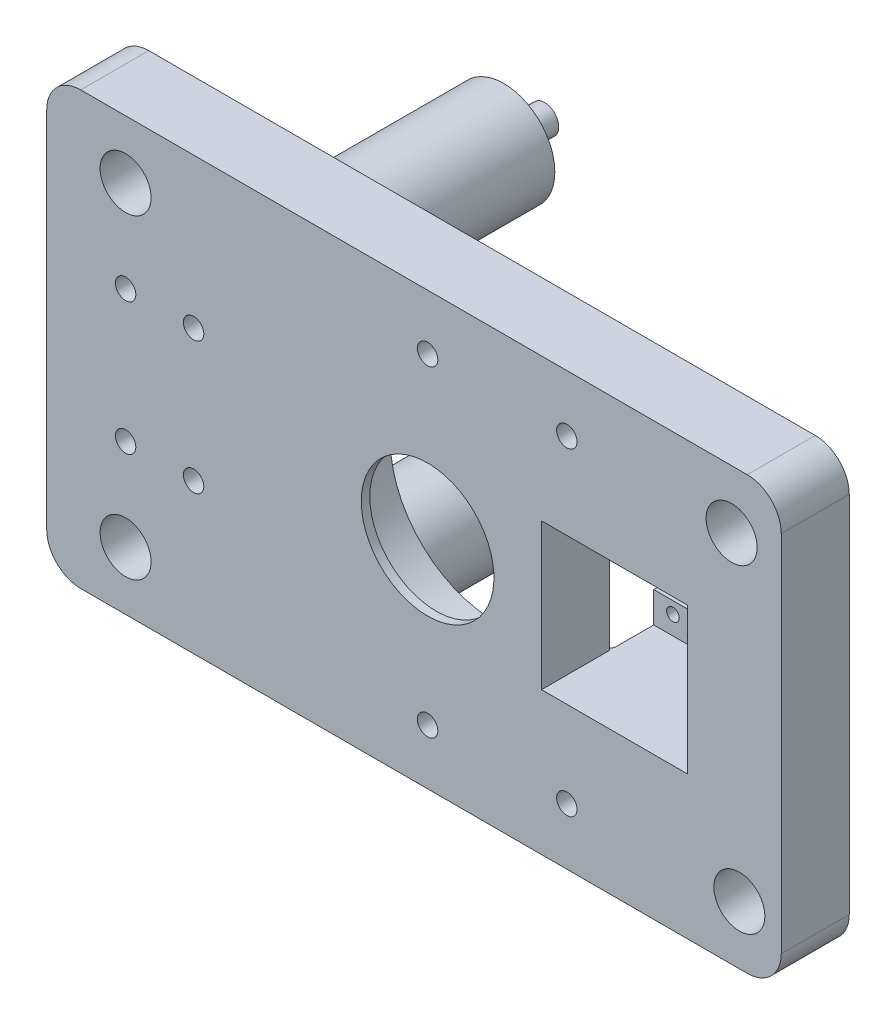
SolidWorks part; units mm, degrees
ref_plane "Front Plane" through (0, 0, 0) normal (0, 0, 1) x (1, 0, 0)
ref_plane "Top Plane" through (0, 0, 0) normal (0, 1, 0) x (1, 0, 0)
ref_plane "Right Plane" through (0, 0, 0) normal (1, 0, 0) x (0, 0, -1)
sketch "Sketch1" plane through (0, 0, 0) normal (0, 0, 1) x (1, 0, 0)
  line L1 (-108, 63.5) -> (108, 63.5)
  line L2 (-108, 63.5) -> (-108, -63.5)
  line L3 (-108, -63.5) -> (108, -63.5)
  line L4 (108, 63.5) -> (108, -63.5)
  line L5 (-108, 63.5) -> (108, -63.5) construction
  line L6 (-108, -63.5) -> (108, 63.5) construction
  point P0 (0, 0)
  dimension "D1" = 127
  dimension "D2" = 216
extrude "Boss-Extrude1" add sketch "Sketch1" along normal blind 20
fillet "Fillet1" radius 10 1 edges at (-108, 63.5, 10)
fillet "Fillet2" radius 10 3 edges at (-108, -63.5, 10) (108, 63.5, 10) (108, -63.5, 10)
sketch "Sketch9" plane through (0, 0, 0) normal (0, 0, -1) x (-1, 0, 0)
  line L0 (-98, 63.5) -> (98, 63.5) construction
  line L1 (-37.5, -21.5) -> (-80.5, -21.5)
  line L2 (-37.5, -21.5) -> (-37.5, 21.5)
  line L3 (-37.5, 21.5) -> (-80.5, 21.5)
  line L4 (-80.5, -21.5) -> (-80.5, 21.5)
  line L5 (-37.5, -21.5) -> (-80.5, 21.5) construction
  line L6 (-37.5, 21.5) -> (-80.5, -21.5) construction
  line L8 (108, 0) -> (-108, 0) construction
  line L9 (108, 53.5) -> (108, -53.5) construction
  line L10 (-108, -53.5) -> (-108, 53.5) construction
  circle A0 centre (-4, 0) radius 31
  point P2 (-59, 0)
  dimension "D6" = 62
  dimension "D1" = 27.5
  dimension "D2" = 55
  dimension "D3" = 43
  dimension "D4" = 43
  dimension "D5" = 63.5
extrude "Cut-Extrude4" cut sketch "Sketch9" against normal blind 17.5 contours A0
sketch "Sketch12" plane through (0, 0, 17.5) normal (0, 0, -1) x (-1, 0, 0)
  circle A0 centre (-4, 0) radius 19.5
  dimension "D1" = 39
extrude "Cut-Extrude5" cut sketch "Sketch12" against normal through all
extrude "Cut-Extrude6" cut sketch "Sketch9<4>" against normal through all contours L3 L4 L1 L2
sketch "Sketch9<4>" plane through (0, 0, 0) normal (0, 0, -1) x (-1, 0, 0) same geometry as "Sketch9"
sketch "Sketch13" plane through (0, 0, 0) normal (0, 0, -1) x (-1, 0, 0)
  line L1 (-37.5, -21.5) -> (-80.5, -21.5)
  line L2 (-37.5, -21.5) -> (-37.5, -25.5)
  line L3 (-37.5, -25.5) -> (-80.5, -25.5)
  line L4 (-80.5, -21.5) -> (-80.5, -25.5)
  dimension "D1" = 4
  dimension "D2" = 43
extrude "Boss-Extrude2" add sketch "Sketch13" along normal blind 17
ref_plane "Plane3" through (0, -21.5, 0) normal (0, 1, 0) x (1, 0, 0)
ref_plane "Plane4" through (0, 0, 0) normal (0, 0, -1) x (-1, 0, 0)
ref_plane "Plane6" through (80.5, 0, 0) normal (1, 0, 0) x (0, 0, -1)
sketch "Sketch16" plane through (80.5, 0, 0) normal (1, 0, 0) x (0, 0, -1)
  line L0 (17, -21.5) -> (0, -21.5) construction
  line L1 (17.0075, -21.5) -> (0.1109, -21.5)
  line L2 (17.0075, -21.5) -> (17.0075, -25.5)
  line L3 (17.0075, -25.5) -> (0.1109, -25.5)
  line L4 (0.1109, -21.5) -> (0.1109, -25.5)
  line L5 (17, -25.5) -> (0, -25.5) construction
fillet "Fillet4" radius 2 3 edges at (59, -25.5, 0) (37.5, -23.5, 0) (80.5, -23.5, 0)
sketch "Sketch17" plane through (0, -21.5, 0) normal (0, 1, 0) x (1, 0, 0)
  line L0 (80.5, 17.0075) -> (80.5, 0.1109) construction
  line L1 (37.5, 17) -> (80.5, 17)
  line L2 (37.5, 17) -> (37.5, 13)
  line L3 (37.5, 13) -> (80.5, 13)
  line L4 (80.5, 17) -> (80.5, 13)
  dimension "D1" = 4
extrude "Boss-Extrude5" add sketch "Sketch17" along normal blind 9
sketch "Sketch18" plane through (0, 0, 0) normal (0, 0, -1) x (-1, 0, 0)
  line L1 (-37.5, 21.5) -> (-80.5, 21.5)
  line L2 (-37.5, 21.5) -> (-37.5, 25.5)
  line L3 (-37.5, 25.5) -> (-80.5, 25.5)
  line L4 (-80.5, 21.5) -> (-80.5, 25.5)
  dimension "D1" = 43
  dimension "D2" = 4
extrude "Boss-Extrude6" add sketch "Sketch18" along normal blind 17
ref_plane "Plane7" through (0, 21.5, 0) normal (0, -1, 0) x (-1, 0, 0)
sketch "Sketch19" plane through (0, 21.5, 0) normal (0, -1, 0) x (-1, 0, 0)
  line L0 (-80.5, 17) -> (-80.5, 0) construction
  line L1 (-37.5, 17) -> (-80.5, 17)
  line L2 (-37.5, 17) -> (-37.5, 13)
  line L3 (-37.5, 13) -> (-80.5, 13)
  line L4 (-80.5, 17) -> (-80.5, 13)
  dimension "D1" = 4
extrude "Boss-Extrude7" add sketch "Sketch19" along normal blind 9
fillet "Fillet5" radius 2 3 edges at (37.5, 23.5, 0) (80.5, 23.5, 0) (59, 25.5, 0)
ref_plane "Plane8" through (0, 0, -17) normal (0, 0, -1) x (-1, 0, 0)
sketch "Sketch20" plane through (0, 0, -17) normal (0, 0, -1) x (-1, 0, 0)
  line L0 (-37.5, -25.5) -> (-37.5, -12.5) construction
  line L2 (-80.5, -21.5) -> (-37.5, -21.5)
  line L3 (-80.5, -12.5) -> (-80.5, -25.5) construction
  line L4 (-80.5, -12.5) -> (-37.5, -12.5) construction
  circle A0 centre (-43.15, -16) radius 1.85
  circle A1 centre (-74.85, -16) radius 1.85
  dimension "D3" = 5.5
  dimension "D4" = 3.7
  dimension "D5" = 5.65
  dimension "D6" = 3.7
  dimension "D1" = 5.65
  dimension "D2" = 9
extrude "Cut-Extrude7" cut sketch "Sketch20" against normal blind 9 contours A1 | A0
ref_plane "Plane9" through (0, 0, -17) normal (0, 0, -1) x (-1, 0, 0)
sketch "Sketch23" plane through (0, 0, -17) normal (0, 0, -1) x (-1, 0, 0)
  line L0 (-37.5, 21.5) -> (-80.5, 21.5)
  line L1 (-37.5, 12.5) -> (-37.5, 25.5) construction
  line L2 (-80.5, 25.5) -> (-80.5, 12.5) construction
  line L3 (-37.5, 12.5) -> (-80.5, 12.5) construction
  circle A0 centre (-43.15, 15.85) radius 1.85
  circle A1 centre (-74.85, 16) radius 1.85
  dimension "D4" = 3.7
  dimension "D5" = 3.7
  dimension "D6" = 5.65
  dimension "D7" = 5.65
  dimension "D1" = 9
  dimension "D2" = 5.5
  dimension "D3" = 5.65
extrude "Cut-Extrude8" cut sketch "Sketch23" against normal blind 9 contours A0 | A1
ref_plane "Plane10" through (0, 0, 0) normal (0, 0, -1) x (-1, 0, 0)
sketch "Sketch25" plane through (0, 0, 0) normal (0, 0, -1) x (-1, 0, 0)
  line L0 (5.8491, 5.5555) -> (-31.0008, -15.2301)
  line L1 (-4, -31) -> (-4, 31)
  line L2 (98, -63.5) -> (-98, -63.5) construction
  line L3 (-98, 63.5) -> (98, 63.5) construction
  circle A0 centre (5.8491, 5.5555) radius 0.0422
  circle A1 centre (-4, 0) radius 31 construction
  circle A2 centre (42.4241, -43.5) radius 15
  circle A3 centre (42.4241, 43.5) radius 15
  point P8 (-12.5759, -4.8373)
  dimension "D4" = 20
  dimension "D5" = 30
  dimension "D6" = 30
  dimension "D1" = 55
  dimension "D2" = 55
  dimension "D3" = 20
extrude "Boss-Extrude9" add sketch "Sketch25" along normal blind 48.84 contours A3 | A2
ref_plane "Plane11" through (0, 0, -48.84) normal (0, 0, -1) x (-1, 0, 0)
sketch "Sketch26" plane through (0, 0, -48.84) normal (0, 0, -1) x (-1, 0, 0)
  circle A0 centre (42.4241, -43.5) radius 4.15
  dimension "D1" = 8.3
extrude "Boss-Extrude10" add sketch "Sketch26" along normal blind 12
ref_plane "Plane12" through (0, 0, -48.84) normal (0, 0, -1) x (-1, 0, 0)
sketch "Sketch27" plane through (0, 0, -48.84) normal (0, 0, -1) x (-1, 0, 0)
  circle A0 centre (42.4241, 43.5) radius 4.15
  dimension "D1" = 8.3
extrude "Boss-Extrude11" add sketch "Sketch27" along normal blind 12
fillet "Fillet9" radius 2 1 edges at (-27.4241, -43.5, 0)
fillet "Fillet10" radius 2 1 edges at (-27.4241, 43.5, 0)
ref_plane "Plane13" through (0, 0, 20) normal (0, 0, 1) x (1, 0, 0)
sketch "Sketch28" plane through (0, 0, 20) normal (0, 0, 1) x (1, 0, 0)
  line L0 (98, 63.5) -> (-98, 63.5) construction
  line L3 (-98, -63.5) -> (98, -63.5) construction
  circle A0 centre (-84.8117, 46.37) radius 7.5
  circle A1 centre (-84.8117, -46.37) radius 7.5
  circle A2 centre (95.674, -46.3698) radius 7.5
  circle A3 centre (93.3991, 46.37) radius 7.5
  dimension "D2" = 15
  dimension "D3" = 17.13
  dimension "D4" = 15
  dimension "D5" = 17.13
  dimension "D6" = 15
  dimension "D7" = 15
  dimension "D1" = 17.13
extrude "Cut-Extrude9" cut sketch "Sketch28" against normal through all
ref_plane "Plane14" through (0, 0, 0) normal (0, 0, -1) x (-1, 0, 0)
sketch "Sketch29" plane through (0, 0, 0) normal (0, 0, -1) x (-1, 0, 0)
  line L0 (-108, 0) -> (108, 0) construction
  line L1 (-108, -53.5) -> (-108, 53.5) construction
  line L2 (108, 53.5) -> (108, -53.5) construction
  line L3 (-4, -31) -> (-4, -63.5) construction
  line L4 (-4, 47.25) -> (-85.8991, 46.37) construction
  line L5 (98, -63.5) -> (-98, -63.5) construction
  line L6 (84.8117, -38.87) -> (84.8117, 0) construction
  line L7 (-4, 31) -> (-4, 63.5) construction
  line L8 (-98, 63.5) -> (98, 63.5) construction
  line L9 (84.8117, 19.435) -> (64.8117, 19.435) construction
  circle A3 centre (-44.9495, 46.81) radius 3
  circle A4 centre (-93.3991, 46.37) radius 7.5 construction
  circle A5 centre (-4, 0) radius 31 construction
  circle A6 centre (-4, 0) radius 31 construction
  circle A7 centre (-4, 47.25) radius 3
  circle A9 centre (-4, -47.25) radius 3
  circle A10 centre (-44.9495, -46.81) radius 3
  circle A11 centre (84.8117, -19.435) radius 3
  circle A12 centre (84.8117, -46.37) radius 7.5 construction
  circle A13 centre (84.8117, 19.435) radius 3
  circle A14 centre (64.8117, 19.435) radius 3
  circle A15 centre (64.8117, -19.435) radius 3
  point P33 (-44.9495, 46.81)
  point P39 (84.8117, -19.435)
  dimension "D1" = 6
  dimension "D2" = 20
extrude "Cut-Extrude11" cut sketch "Sketch29" against normal through all contours A7 | A11 | A9 | A14 | A13 | A15 | A3 | A10
ref_plane "Plane15" through (0, 0, 10) normal (0, 0, -1) x (-1, 0, 0)
